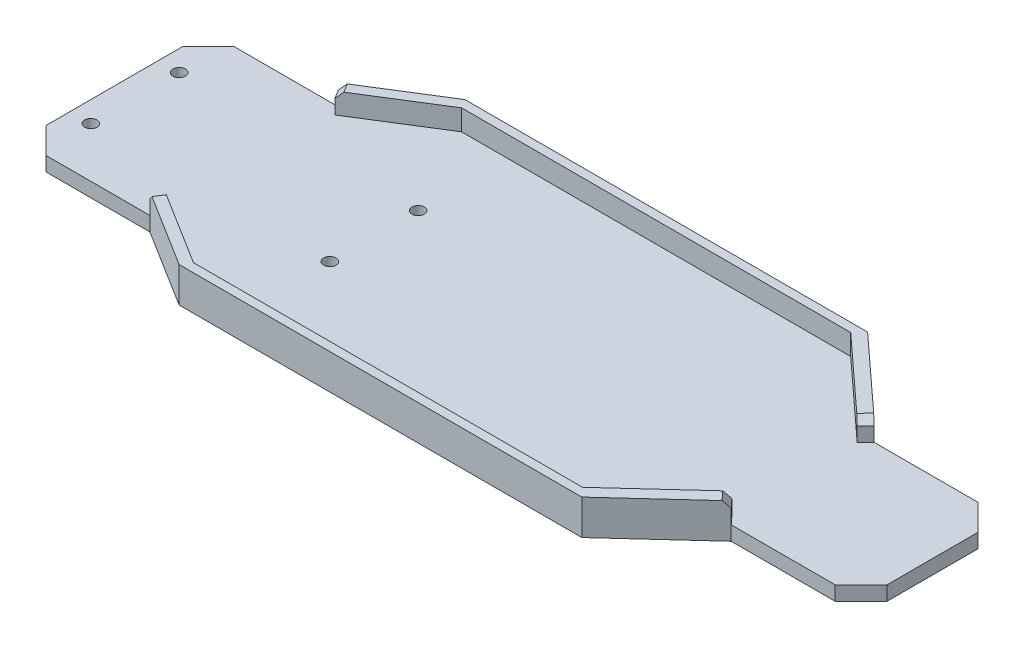
SolidWorks part; units mm, degrees
material "PETG - Polymaker"
ref_plane "Front Plane" through (0, 0, 0) normal (0, 0, 1) x (1, 0, 0)
ref_plane "Top Plane" through (0, 0, 0) normal (0, 1, 0) x (1, 0, 0)
ref_plane "Right Plane" through (0, 0, 0) normal (1, 0, 0) x (0, 0, -1)
sketch "Sketch1" plane through (0, 0, 0) normal (0, 1, 0) x (1, 0, 0)
  line L0 (-235.1499, 0) -> (235.1499, 0) construction
  line L1 (0, 0) -> (0, 52596.8311) construction
  line L2 (-107.5, 36.25) -> (-77.5, 55)
  line L3 (-77.5, 55) -> (77.5, 55)
  line L4 (-107.5, 36.25) -> (-157.5, 36.25)
  line L5 (-157.5, 36.25) -> (-157.5, -36.25)
  line L6 (-77.5, -55) -> (77.5, -55)
  line L7 (-107.5, -36.25) -> (-77.5, -55)
  line L8 (-107.5, -36.25) -> (-157.5, -36.25)
  line L9 (77.5, 55) -> (107.5, 27.5)
  line L10 (107.5, 27.5) -> (157.5, 27.5)
  line L11 (157.5, 27.5) -> (157.5, -27.5)
  line L12 (107.5, -27.5) -> (157.5, -27.5)
  line L13 (77.5, -55) -> (107.5, -27.5)
  point P3 (0, 0)
  point P10 (-92.5, 45.625)
  point P15 (-92.5, -45.625)
  point P18 (-157.5, 0)
  point P19 (0, -55)
  point P20 (0, 55)
  point P23 (157.5, 0)
  dimension "D1" = 55
  dimension "D2" = 72.5
  dimension "D3" = 30
  dimension "D4" = 50
  dimension "D5" = 155
  dimension "D6" = 50
  dimension "D7" = 55
  dimension "D8" = 30
  dimension "D9" = 110
extrude "Boss-Extrude1" add sketch "Sketch1" along normal blind 5.5
sketch "Sketch3" plane through (0, 5.5, 0) normal (0, 1, 0) x (1, 0, 0)
  line L0 (0, 0) -> (50000, 0) construction
  line L1 (0, 0) -> (0, 50000) construction
  line L2 (0, 55) -> (-77.5, 55)
  line L3 (77.5, 55) -> (-77.5, 55) construction
  line L4 (-77.5, 55) -> (-107.5, 36.25)
  line L5 (-107.5, 36.25) -> (-105.38, 32.858)
  line L6 (-105.38, 32.858) -> (-75.38, 51.608)
  line L7 (-75.38, 51.608) -> (0, 51.608)
  line L8 (-77.5, 55) -> (-75.38, 51.608) construction
  line L9 (0, 55) -> (77.5, 55)
  line L10 (77.5, 55) -> (107.5, 27.5)
  line L11 (107.5, 27.5) -> (104.3907, 24.108)
  line L12 (104.3907, 24.108) -> (74.3907, 51.608)
  line L13 (74.3907, 51.608) -> (0, 51.608)
  line L14 (74.3907, 51.608) -> (77.5, 55) construction
  line L15 (74.3907, -51.608) -> (77.5, -55) construction
  line L16 (-77.5, -55) -> (-75.38, -51.608) construction
  line L17 (74.3907, -51.608) -> (0, -51.608)
  line L18 (104.3907, -24.108) -> (74.3907, -51.608)
  line L19 (107.5, -27.5) -> (104.3907, -24.108)
  line L20 (77.5, -55) -> (107.5, -27.5)
  line L21 (0, -55) -> (77.5, -55)
  line L22 (-75.38, -51.608) -> (0, -51.608)
  line L23 (-105.38, -32.858) -> (-75.38, -51.608)
  line L24 (-107.5, -36.25) -> (-105.38, -32.858)
  line L25 (-77.5, -55) -> (-107.5, -36.25)
  line L26 (0, -55) -> (-77.5, -55)
  dimension "D1" = 4
extrude "Chassis-Walls1" add sketch "Sketch3" along normal blind 8
chamfer "Chamfer1" distance 10 angle 45 2 edges at (-157.5, 2.75, -36.25) (-157.5, 2.75, 36.25)
chamfer "Chamfer2" distance 10 angle 45 2 edges at (157.5, 2.75, -27.5) (157.5, 2.75, 27.5)
chamfer "Chamfer3" distance 2.5 angle 45 4 edges at (-106.44, 13.5, -34.554) (-106.44, 13.5, 34.554) (105.9453, 13.5, 25.804) (105.9453, 13.5, -25.804)
sketch "Sketch4" plane through (0, 0, 0) normal (0, -1, 0) x (1, 0, 0)
  line L0 (0, 0) -> (50000, 0) construction
  line L1 (-149.5, 17) -> (-57.5, 17) construction
  line L2 (-157.5, -26.25) -> (-157.5, 26.25) construction
  circle A0 centre (-149.5, 17) radius 2.4
  circle A1 centre (-57.5, 17) radius 2.4
  circle A2 centre (-57.5, -17) radius 2.4
  circle A3 centre (-149.5, -17) radius 2.4
  dimension "D1" = 4.8
  dimension "D2" = 4.8
  dimension "D3" = 8
  dimension "D4" = 92
  dimension "D5" = 34
extrude "Cut-Extrude1" cut sketch "Sketch4" against normal blind 10
